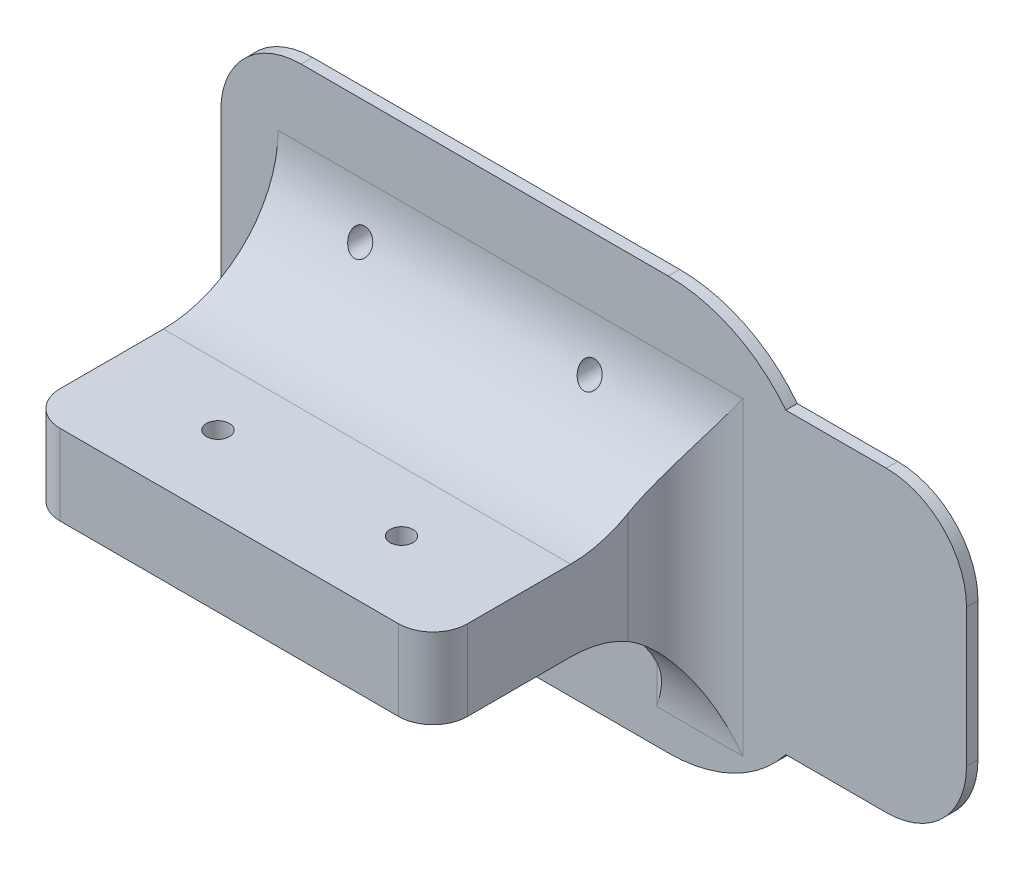
SolidWorks part; units mm, degrees
ref_plane "Front Plane" through (0, 0, 0) normal (0, 0, 1) x (1, 0, 0)
ref_plane "Top Plane" through (0, 0, 0) normal (0, 1, 0) x (1, 0, 0)
ref_plane "Right Plane" through (0, 0, 0) normal (1, 0, 0) x (0, 0, -1)
sketch "Sketch1" plane through (0, 0, 0) normal (0, 0, 1) x (1, 0, 0)
  line L0 (-18, 11) -> (-18, -11)
  line L1 (-16, -13) -> (16, -13)
  line L2 (-16, 13) -> (16, 13)
  line L3 (24.6603, 8) -> (35, 8)
  line L4 (55, 0) -> (-55, 0) construction
  line L5 (24.6603, -8) -> (35, -8)
  line L6 (37, 6) -> (37, -6)
  arc A0 (16, 13) -> (22.9282, 9) centre (16, 5) cw
  arc A1 (22.9282, 9) -> (24.6603, 8) centre (24.6603, 10) ccw
  arc A2 (22.9282, -9) -> (24.6603, -8) centre (24.6603, -10) cw
  arc A3 (16, -13) -> (22.9282, -9) centre (16, -5) ccw
  arc A4 (35, -8) -> (37, -6) centre (35, -6) ccw
  arc A5 (35, 8) -> (37, 6) centre (35, 6) cw
  arc A6 (-18, -11) -> (-16, -13) centre (-16, -11) ccw
  arc A7 (-18, 11) -> (-16, 13) centre (-16, 11) cw
  point P5 (-18, 0)
  point P7 (0, 13)
  point P21 (37, -8)
  point P24 (37, 8)
  point P27 (-18, -13)
  point P30 (-18, 13)
  point P31 (37, 0)
  dimension "D3" = 2
  dimension "D4" = 2
  dimension "D7" = 8
  dimension "D8" = 2
  dimension "D1" = 26
  dimension "D2" = 34
  dimension "D5" = 16
  dimension "D6" = 55
extrude "Insert in sheet metal hole" add sketch "Sketch1" along normal blind 1
sketch "Sketch10" plane through (0, 0, 1) normal (0, 0, 1) x (1, 0, 0)
  line L12 (26.247, -13) -> (35, -13)
  line L13 (42, -6) -> (42, 6)
  line L14 (35, 13) -> (26.247, 13)
  line L15 (16, 18) -> (-16, 18)
  line L16 (-23, 11) -> (-23, -11)
  line L17 (-16, -18) -> (16, -18)
  line L18 (26.247, -13) -> (35, -13)
  line L19 (42, -6) -> (42, 6)
  line L20 (35, 13) -> (26.247, 13)
  line L21 (16, 18) -> (-16, 18)
  line L22 (-23, 11) -> (-23, -11)
  line L23 (-16, -18) -> (16, -18)
  arc A16 (16, -18) -> (26.247, -13) centre (16, -5) ccw
  arc A17 (35, -13) -> (42, -6) centre (35, -6) ccw
  arc A18 (42, 6) -> (35, 13) centre (35, 6) ccw
  arc A19 (26.247, 13) -> (16, 18) centre (16, 5) ccw
  arc A20 (-16, 18) -> (-23, 11) centre (-16, 11) ccw
  arc A21 (-23, -11) -> (-16, -18) centre (-16, -11) ccw
  arc A22 (16, -18) -> (26.247, -13) centre (16, -5) ccw
  arc A23 (35, -13) -> (42, -6) centre (35, -6) ccw
  arc A24 (42, 6) -> (35, 13) centre (35, 6) ccw
  arc A25 (26.247, 13) -> (16, 18) centre (16, 5) ccw
  arc A26 (-16, 18) -> (-23, 11) centre (-16, 11) ccw
  arc A27 (-23, -11) -> (-16, -18) centre (-16, -11) ccw
  dimension "D1" = 5
extrude "Boss-Extrude5" add sketch "Sketch10" along normal blind 1
sketch "Sketch2" plane through (-18, 0, 0) normal (-1, 0, 0) x (0, 0, 1)
  line L0 (0, 2) -> (24, 2)
  line L2 (24, 2) -> (24, 0)
  line L3 (24, 0) -> (0, 0)
  line L4 (0, 0) -> (0, 2)
  line L5 (0, 11) -> (0, -11) construction
  line L6 (2, 11) -> (2, -11) construction
  dimension "D1" = 22
  dimension "D2" = 2
extrude "LED backing" add sketch "Sketch2" against normal up to surface (55 mm away) up to face at (37, 0, 0.5)
sketch "Sketch3" plane through (0, 0, 0) normal (0, -1, 0) x (1, 0, 0)
  line L0 (-8, 2) -> (-8, 17.25) construction
  line L2 (-8, 17.25) -> (8, 17.25) construction
  line L3 (8, 17.25) -> (8, 2) construction
  line L5 (37, 2) -> (-18, 2) construction
  circle A0 centre (-8, 17.25) radius 1
  circle A1 centre (8, 17.25) radius 1
  point P10 (0, 17.25)
  dimension "D1" = 2
  dimension "D2" = 15.25
  dimension "D3" = 16
extrude "LED screwholes" cut sketch "Sketch3" against normal blind 10
sketch "Sketch5" plane through (0, 0, 0) normal (0, -1, 0) x (1, 0, 0)
  line L1 (37, 2) -> (-18, 2) construction
  line L8 (37, 24) -> (17.5, 24)
  line L9 (37, 24) -> (37, 2)
  line L10 (37, 2) -> (17.5, 2)
  line L11 (17.5, 24) -> (17.5, 2)
  circle A2 centre (8, 17.25) radius 1 construction
  dimension "D1" = 9.5
extrude "LED backing cleanup" cut sketch "Sketch5" against normal through all both and the other way through all
fillet "Fillet1" radius 3 2 edges at (17.5, 1, 24) (-18, 1, 24)
sketch "Sketch6" plane through (0, 0, 0) normal (0, -1, 0) x (1, 0, 0)
  line L17 (14.5, 24) -> (-15, 24)
  line L18 (17.5, 2) -> (17.5, 21)
  line L19 (-18, 2) -> (17.5, 2)
  line L20 (-18, 21) -> (-18, 2)
  line L22 (14.5, 24) -> (-15, 24)
  line L23 (17.5, 2) -> (17.5, 21)
  line L24 (-18, 2) -> (-16.5, 2)
  line L25 (-18, 21) -> (-18, 2)
  line L26 (-16.5, 3.5) -> (-16.5, 2)
  line L27 (16, 3.5) -> (16, 2)
  line L28 (16, 2) -> (17.5, 2)
  line L30 (14.5, 22.5) -> (-15, 22.5)
  line L31 (16, 3.5) -> (16, 21)
  line L32 (-16.5, 3.5) -> (16, 3.5)
  line L33 (-16.5, 21) -> (-16.5, 3.5)
  line L34 (14.5, 22.5) -> (-15, 22.5)
  line L35 (16, 3.5) -> (16, 21)
  line L37 (-16.5, 21) -> (-16.5, 3.5)
  arc A8 (17.5, 21) -> (14.5, 24) centre (14.5, 21) ccw
  arc A9 (-15, 24) -> (-18, 21) centre (-15, 21) ccw
  arc A10 (17.5, 21) -> (14.5, 24) centre (14.5, 21) ccw
  arc A11 (-15, 24) -> (-18, 21) centre (-15, 21) ccw
  arc A14 (16, 21) -> (14.5, 22.5) centre (14.5, 21) ccw
  arc A15 (-15, 22.5) -> (-16.5, 21) centre (-15, 21) ccw
  arc A16 (16, 21) -> (14.5, 22.5) centre (14.5, 21) ccw
  arc A17 (-15, 22.5) -> (-16.5, 21) centre (-15, 21) ccw
  dimension "D1" = 0
  dimension "D2" = 1.5
extrude "Boss-Extrude3" add sketch "Sketch6" along normal blind 5
fillet "Fillet2" radius 10 3 edges at (-0.25, 2, 2) (16.75, -5, 2) (-17.25, -5, 2)
fillet "Fillet3" radius 5 1 edges at (17.5, -1.5, 2)
fillet "Fillet4" radius 1 8 edges at (-16.5, 0, 11.5) (-16.0607, 0, 22.0607) (16, 0, 11.5) (15.5607, 0, 22.0607) (-0.25, 0, 22.5) (-16.5, -7.5, 2) (-0.25, 0, 2) (16, -7.5, 2)
sketch "Sketch7" plane through (0, 0, 2) normal (0, 0, 1) x (1, 0, 0)
  line L3 (15, -1) -> (-15.5, -1) construction
  line L4 (15, -15) -> (15, -1) construction
  line L5 (-15.5, -1) -> (-15.5, -15) construction
  circle A0 centre (-13, -3.5) radius 2.5
  circle A1 centre (12.5, -3.5) radius 2.5
  dimension "D1" = 5
extrude "LED wire holes" cut sketch "Sketch7" against normal through all
sketch "Sketch8" plane through (0, 0, 2) normal (0, 0, 1) x (1, 0, 0)
  line L2 (16, 18) -> (-16, 18) construction
  line L3 (-16, -18) -> (16, -18) construction
  circle A0 centre (0, -8) radius 1
  circle A1 centre (-10, 8) radius 1
  circle A2 centre (10, 8) radius 1
  dimension "D1" = 2
  dimension "D2" = 20
  dimension "D3" = 10
  dimension "D4" = 10
  dimension "D5" = 10
extrude "Screwholes for backing" cut sketch "Sketch8" against normal through all both and the other way through all
sketch "Sketch9" plane through (0, 0, 2) normal (0, 0, 1) x (1, 0, 0)
  line L1 (-5, -1.75) -> (5, -1.75)
  line L2 (-5, -1.75) -> (-5, -3.75)
  line L3 (-5, -3.75) -> (5, -3.75)
  line L4 (5, -1.75) -> (5, -3.75)
  line L5 (-16, 0) -> (15, 0) construction
  line L6 (-15.5, 0) -> (15, 0) construction
  point P6 (0, -1.75)
  dimension "D1" = 2
  dimension "D2" = 1.75
  dimension "D3" = 10
extrude "Boss-Extrude4" add sketch "Sketch9" along normal blind 1
fillet "Fillet5" radius 3 3 edges at (5, -2.75, 2) (-5, -2.75, 2) (0, -3.75, 2)
